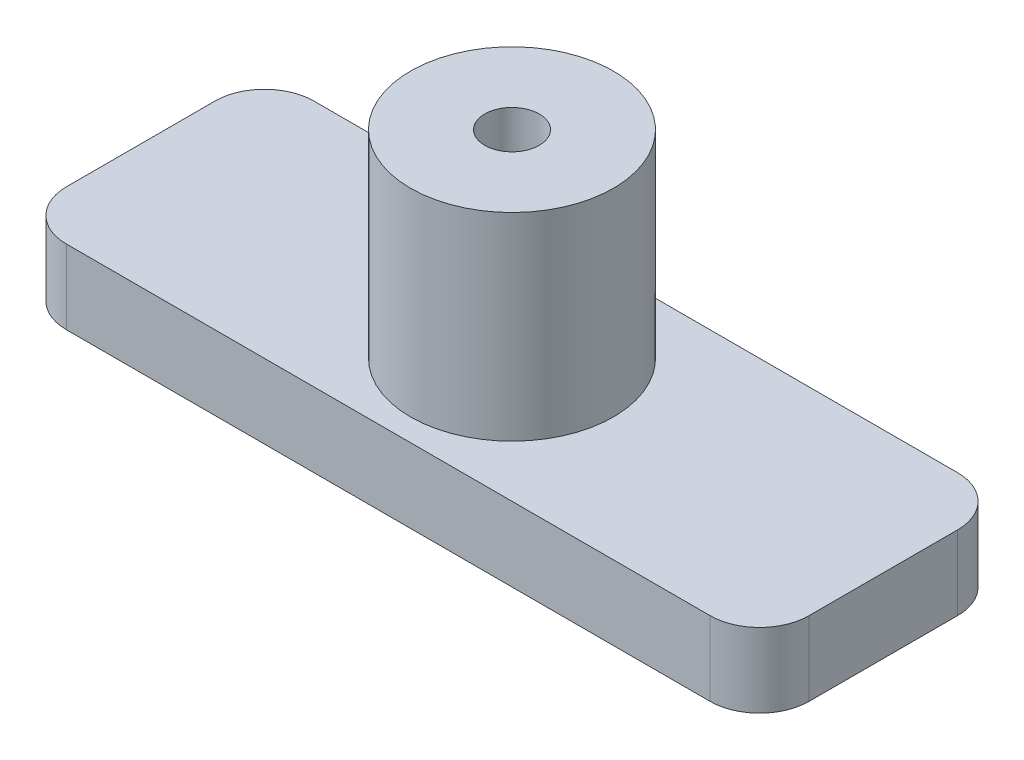
SolidWorks part; units mm, degrees
ref_plane "Front Plane" through (0, 0, 0) normal (0, 0, 1) x (1, 0, 0)
ref_plane "Top Plane" through (0, 0, 0) normal (0, 1, 0) x (1, 0, 0)
ref_plane "Right Plane" through (0, 0, 0) normal (1, 0, 0) x (0, 0, -1)
sketch "Sketch1" plane through (0, 0, 0) normal (0, 1, 0) x (1, 0, 0)
  line L1 (15, -5) -> (-15, -5)
  line L2 (15, -5) -> (15, 5)
  line L3 (15, 5) -> (-15, 5)
  line L4 (-15, -5) -> (-15, 5)
  line L5 (15, -5) -> (-15, 5) construction
  line L6 (15, 5) -> (-15, -5) construction
  point P0 (0, 0)
  dimension "D1" = 30
  dimension "D2" = 10
extrude "Boss-Extrude1" add sketch "Sketch1" along normal blind 3
sketch "Sketch2" plane through (0, 3, 0) normal (0, 1, 0) x (1, 0, 0)
  circle A0 centre (0, 0) radius 4.1
  circle A1 centre (0, 0) radius 1.1
  dimension "D1" = 3
  dimension "D2" = 2.2
extrude "Boss-Extrude2" add sketch "Sketch2" along normal blind 8
fillet "Fillet1" radius 2 4 edges at (15, 1.5, -5) (15, 1.5, 5) (-15, 1.5, -5) (-15, 1.5, 5)
